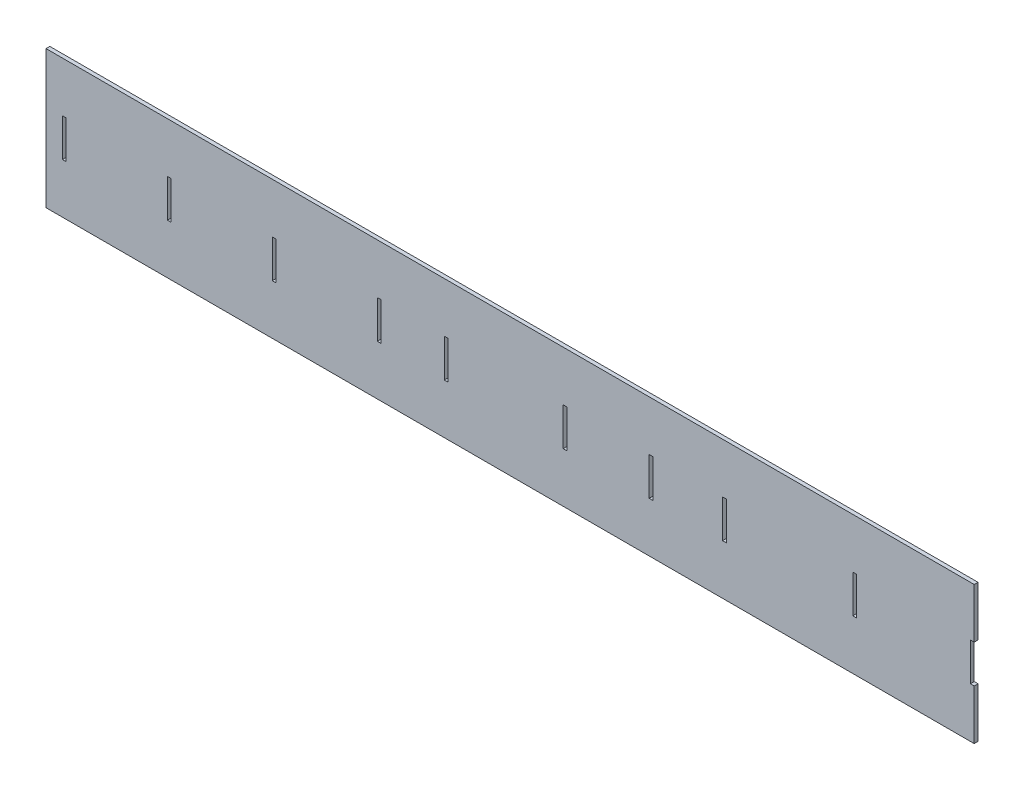
SolidWorks part; units mm, degrees
ref_plane "Front Plane" through (0, 0, 0) normal (0, 0, 1) x (1, 0, 0)
ref_plane "Top Plane" through (0, 0, 0) normal (0, 1, 0) x (1, 0, 0)
ref_plane "Right Plane" through (0, 0, 0) normal (1, 0, 0) x (0, 0, -1)
sketch "Sketch1" plane through (0, 0, 0) normal (0, 0, 1) x (1, 0, 0)
  line L1 (110.3511, 109) -> (844.3511, 109)
  line L3 (844.3511, 0) -> (110.3511, 0)
  line L4 (1244.614, 54.5) -> (110.3511, 54.5) construction
  line L5 (123.3511, 69.5) -> (126.3511, 69.5)
  line L6 (123.3511, 69.5) -> (123.3511, 39.5)
  line L7 (123.3511, 39.5) -> (126.3511, 39.5)
  line L8 (126.3511, 69.5) -> (126.3511, 39.5)
  line L14 (206.3511, 69.5) -> (209.3511, 69.5)
  line L15 (206.3511, 69.5) -> (206.3511, 39.5)
  line L16 (206.3511, 39.5) -> (209.3511, 39.5)
  line L17 (209.3511, 69.5) -> (209.3511, 39.5)
  line L18 (289.3511, 69.5) -> (292.3511, 69.5)
  line L19 (289.3511, 69.5) -> (289.3511, 39.5)
  line L20 (289.3511, 39.5) -> (292.3511, 39.5)
  line L21 (292.3511, 69.5) -> (292.3511, 39.5)
  line L22 (372.3511, 69.5) -> (375.3511, 69.5)
  line L23 (372.3511, 69.5) -> (372.3511, 39.5)
  line L24 (372.3511, 39.5) -> (375.3511, 39.5)
  line L25 (375.3511, 69.5) -> (375.3511, 39.5)
  line L26 (425.3511, 69.5) -> (428.3511, 69.5)
  line L27 (425.3511, 69.5) -> (425.3511, 39.5)
  line L28 (425.3511, 39.5) -> (428.3511, 39.5)
  line L29 (428.3511, 69.5) -> (428.3511, 39.5)
  line L30 (519.3511, 69.5) -> (522.3511, 69.5)
  line L31 (519.3511, 69.5) -> (519.3511, 39.5)
  line L32 (519.3511, 39.5) -> (522.3511, 39.5)
  line L33 (522.3511, 69.5) -> (522.3511, 39.5)
  line L34 (587.3511, 69.5) -> (590.3511, 69.5)
  line L35 (587.3511, 69.5) -> (587.3511, 39.5)
  line L36 (587.3511, 39.5) -> (590.3511, 39.5)
  line L37 (590.3511, 69.5) -> (590.3511, 39.5)
  line L38 (645.3511, 69.5) -> (648.3511, 69.5)
  line L39 (645.3511, 69.5) -> (645.3511, 39.5)
  line L40 (645.3511, 39.5) -> (648.3511, 39.5)
  line L41 (648.3511, 69.5) -> (648.3511, 39.5)
  line L42 (748.3511, 69.5) -> (751.3511, 69.5)
  line L43 (748.3511, 69.5) -> (748.3511, 39.5)
  line L44 (748.3511, 39.5) -> (751.3511, 39.5)
  line L45 (751.3511, 69.5) -> (751.3511, 39.5)
  line L46 (841.3511, 69.5) -> (844.3511, 69.5)
  line L47 (841.3511, 69.5) -> (841.3511, 39.5)
  line L48 (841.3511, 39.5) -> (844.3511, 39.5)
  line L53 (844.3511, 69.5) -> (844.3511, 109)
  line L54 (844.3511, 39.5) -> (844.3511, 0)
  line L55 (110.3511, 109) -> (110.3511, 0)
  dimension "D1" = 109
  dimension "D2" = 30
  dimension "D3" = 3
  dimension "D4" = 13
  dimension "D8" = 30
  dimension "D9" = 3
  dimension "D10" = 30
  dimension "D11" = 3
  dimension "D12" = 80
  dimension "D13" = 80
  dimension "D14" = 80
  dimension "D15" = 3
  dimension "D16" = 30
  dimension "D17" = 50
  dimension "D18" = 3
  dimension "D19" = 30
  dimension "D20" = 91
  dimension "D21" = 3
  dimension "D22" = 30
  dimension "D23" = 65
  dimension "D24" = 30
  dimension "D25" = 3
  dimension "D26" = 55
  dimension "D27" = 3
  dimension "D28" = 30
  dimension "D29" = 3
  dimension "D30" = 30
  dimension "D31" = 100
  dimension "D32" = 90
  dimension "D33" = 3
  dimension "D34" = 30
extrude "Boss-Extrude1" add sketch "Sketch1" along normal blind 3
